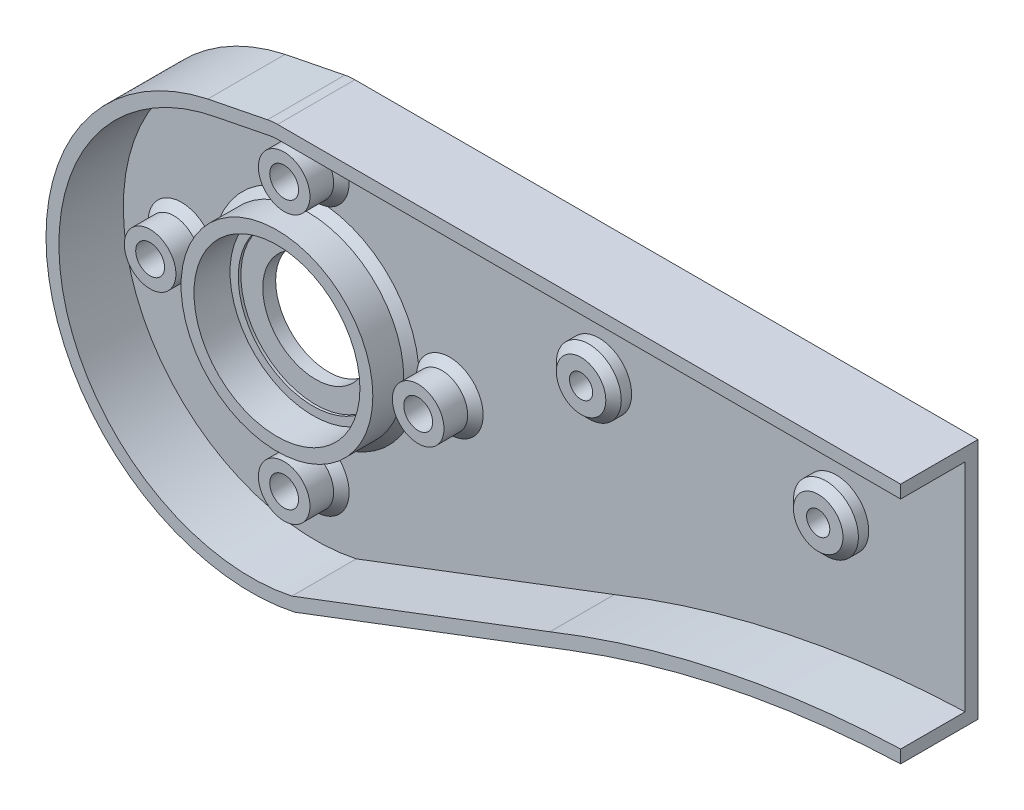
SolidWorks part; units mm, degrees
material "ABS generico"
ref_plane "Piano frontale" through (0, 0, 0) normal (0, 0, 1) x (1, 0, 0)
ref_plane "Piano superiore" through (0, 0, 0) normal (0, 1, 0) x (1, 0, 0)
ref_plane "Piano destro" through (0, 0, 0) normal (1, 0, 0) x (0, 0, -1)
sketch "Schizzo1" plane through (0, 0, 0) normal (0, 0, 1) x (1, 0, 0)
  line L0 (5.1235, 41.4) -> (126, 41.4)
  line L1 (-8.4161, 38.9) -> (3.1704, 41.2074)
  line L2 (46, 26.4263) -> (46, 7.4358) construction
  line L3 (46, 7.4358) -> (126, 7.4358) construction
  line L4 (55, 17.9) -> (101, 17.9) construction
  line L5 (126, 41.4) -> (126, -5.6)
  line L6 (126, -5.6) -> (96, -5.6) construction
  line L7 (8.4161, -38.9) -> (96, -5.6) construction
  line L8 (8.4161, -38.9) -> (-8.4161, 38.9) construction
  line L10 (126, 38.9) -> (5.37, 38.9)
  line L11 (3.4169, 38.7074) -> (-6.661, 36.7004)
  line L12 (7.8874, -36.4565) -> (57.9534, -17.4211)
  line L13 (95.62, -3.1) -> (126, -3.1) construction
  line L14 (61.9889, -18.5312) -> (61.1104, -16.2208) construction
  line L15 (61.9889, -18.5312) -> (133.0662, -205.4751) construction
  line L16 (61.1104, -16.2208) -> (95.62, -3.1) construction
  line L17 (61.9889, -18.5312) -> (8.4161, -38.9)
  arc A0 (-8.4161, 38.9) -> (8.4161, -38.9) centre (0, 0) ccw
  circle A1 centre (55, 17.9) radius 8.0303 construction
  circle A2 centre (101, 17.9) radius 6.341 construction
  arc A3 (-6.661, 36.7004) -> (7.8874, -36.4565) centre (0, 0) ccw
  arc A4 (126, -5.6) -> (61.9889, -18.5312) centre (133.0662, -205.4751) ccw
  arc A5 (126, -3.0985) -> (57.9534, -17.4211) centre (133.0662, -205.4751) ccw
  arc A6 (5.37, 38.9) -> (3.4169, 38.7074) centre (5.37, 28.9) ccw
  arc A7 (5.1235, 41.4) -> (3.1704, 41.2074) centre (5.1235, 31.4) ccw
  point P31 (4.1374, 41.4)
  dimension "D1" = 79.6
  dimension "D4" = 23.5
  dimension "D10" = 25
  dimension "D12" = 2.5
  dimension "D15" = 400
  dimension "D18" = 2.5
  dimension "D19" = 10
  dimension "D2" = 55
  dimension "D3" = 17.9
  dimension "D5" = 12.8
  dimension "D6" = 2.5
  dimension "D7" = 9
  dimension "D8" = 80
  dimension "D9" = 25
  dimension "D11" = 30
  dimension "D13" = 47
  dimension "D14" = 2.5
  dimension "D16" = 2.5
  dimension "D17" = 2.5
extrude "Estrusione-Estrusione1" add sketch "Schizzo1" along normal blind 2.5 contours L1 A0 L7 L6 L5 L0 | L11 A3 L12 L13 L10 region at (65.5617, 39.5538, 0) region at (38.9448, 7.3337, 0)
extrude "Estrusione-Estrusione2" add sketch "Schizzo1<3>" along normal blind 15 contours A3 L11 L10 L5 L0 L1 A0 L7 L6 L13 L12 region at (65.5617, 39.5538, 0)
sketch "Schizzo1<3>" plane through (0, 0, 0) normal (0, 0, 1) x (1, 0, 0) same geometry as "Schizzo1"
sketch "Schizzo2" plane through (0, 0, 0) normal (0, 0, -1) x (-1, 0, 0)
  line L0 (-26, 0) -> (26, 0) construction
  line L1 (0, -26) -> (0, 26) construction
  circle A0 centre (0, 0) radius 10.25
  circle A1 centre (0, 0) radius 26 construction
  circle A2 centre (0, -26) radius 2.8
  circle A3 centre (26, 0) radius 2.8
  circle A4 centre (0, 26) radius 2.8
  circle A5 centre (-26, 0) radius 2.8 construction
  dimension "D1" = 5.6
  dimension "D2" = 52
  dimension "D3" = 20.5
extrude "Taglio-Estrusione1" cut sketch "Schizzo2" against normal blind 15
sketch "Schizzo3" plane through (0, 0, 2.5) normal (0, 0, 1) x (1, 0, 0)
  line L0 (126, 38.9) -> (126, -3.0985) construction
  line L1 (55, 17.9) -> (101, 17.9) construction
  line L2 (26, 0) -> (0, 0) construction
  circle A0 centre (0, 0) radius 14.5
  circle A1 centre (0, 0) radius 16.1
  circle A2 centre (0, 0) radius 18.6
  circle A3 centre (0, 26) radius 2.8
  circle A4 centre (0, 26) radius 5
  circle A5 centre (26, 0) radius 2.8
  circle A6 centre (26, 0) radius 5
  circle A7 centre (0, -26) radius 2.8
  circle A8 centre (0, -26) radius 5
  circle A9 centre (-26, 0) radius 2.8
  circle A10 centre (-26, 0) radius 5
  circle A11 centre (55, 17.9) radius 6.3
  circle A12 centre (101, 17.9) radius 6.3
  circle A13 centre (55, 17.9) radius 2.25
  circle A14 centre (101, 17.9) radius 2.25
  circle M12 centre (0, -26) radius 2.8
  circle M13 centre (-26, 0) radius 2.8
  circle M14 centre (0, 26) radius 2.8
  dimension "D1" = 29
  dimension "D2" = 32.2
  dimension "D3" = 37.2
  dimension "D4" = 10
  dimension "D5" = 5.6
  dimension "D6" = 12.6
  dimension "D10" = 4.5
  dimension "D7" = 25
  dimension "D8" = 55
  dimension "D9" = 17.9
  dimension "D11" = 26
extrude "Estrusione-Estrusione3" add sketch "Schizzo3" along normal blind 0.5 contours A1 A0 region at (-15.6446, 0, 2.5)
extrude "Estrusione-Estrusione4" add sketch "Schizzo3<3>" along normal blind 7.5 contours A2 A1 region at (-18.0739, 0, 2.5)
sketch "Schizzo3<3>" plane through (0, 0, 2.5) normal (0, 0, 1) x (1, 0, 0) same geometry as "Schizzo3"
extrude "Estrusione-Estrusione5" add sketch "Schizzo3<4>" along normal blind 6.1 contours A10 M13 | A8 M12 | A6 | A4 M14 region at (-4.8586, 26, 2.5) region at (21.1414, 0, 2.5) region at (-4.8586, -26, 2.5) region at (-30.8586, 0, 2.5)
sketch "Schizzo3<4>" plane through (0, 0, 2.5) normal (0, 0, 1) x (1, 0, 0) same geometry as "Schizzo3"
extrude "Estrusione-Estrusione6" add sketch "Schizzo3<5>" along normal blind 3.5 contours A13 A11 | A12 A14 region at (48.8782, 17.9, 2.5) region at (94.8782, 17.9, 2.5)
sketch "Schizzo3<5>" plane through (0, 0, 2.5) normal (0, 0, 1) x (1, 0, 0) same geometry as "Schizzo3"
chamfer "Smusso1" distance 1.5 angle 45 7 edges at (18.6, 0, 2.5) (5, -26, 2.5) (31, 0, 2.5) (5, 26, 2.5) (-21, 0, 2.5) (107.3, 17.9, 6) (61.3, 17.9, 6)
hole_wizard "Foro per Vite M4-1" positions "Schizzo3D1" profile "Schizzo5" hole size "M4" standard "ISO"
sketch3d "Schizzo3D1"
  line L0 (101, 17.9, 0) -> (55, 17.9, 0) construction
  line L2 (126, 41.4, 0) -> (126, -5.6, 0) construction
  line L3 (0, 0, 0) -> (0, 47.825, 0) construction
  point P1 (55, 17.9, 0)
  point P3 (101, 17.9, 0)
  dimension "D1" = 25
  dimension "D2" = 55
  dimension "D3" = 17.9
sketch "Schizzo5" plane through (55, 17.9, 0) normal (1, 0, 0) x (0, 1, 0)
  line L0 (0, 0) -> (0, 51.3519)
  line L1 (0, 51.3519) -> (2.25, 50)
  line L2 (2.25, 50) -> (2.25, 0)
  line L5 (2.25, 0) -> (0, 0)
  line L10 (0, 51.3519) -> (-2.25, 50) construction
  line L11 (0, -6.35) -> (0, 107.95) construction
  dimension "Hole Dia." = 4.5
  dimension "Hole Depth" = 50
  dimension "Drill Angle" = 118
